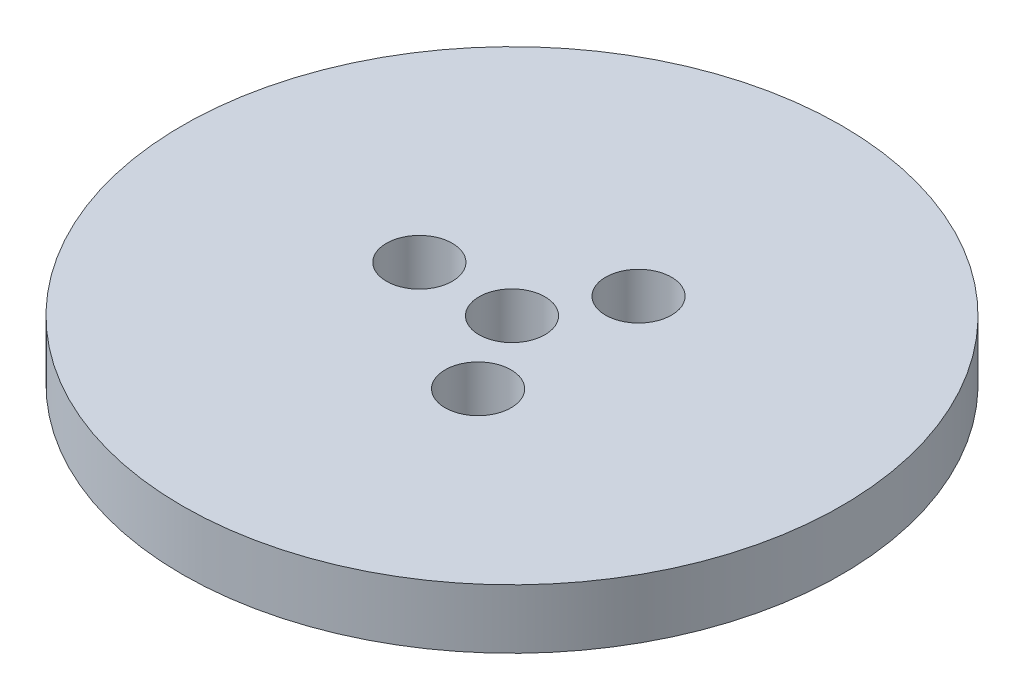
SolidWorks part; units mm, degrees
ref_plane "Front Plane" through (0, 0, 0) normal (0, 0, 1) x (1, 0, 0)
ref_plane "Top Plane" through (0, 0, 0) normal (0, 1, 0) x (1, 0, 0)
ref_plane "Right Plane" through (0, 0, 0) normal (1, 0, 0) x (0, 0, -1)
sketch "Sketch1" plane through (0, 0, 0) normal (0, 1, 0) x (1, 0, 0)
  circle A0 centre (0, 0) radius 100
  dimension "FLANGE_OD" = 200
extrude "Boss-Extrude1" add sketch "Sketch1" along normal blind 18
sketch "Sketch2" plane through (0, 0, 0) normal (0, 1, 0) x (1, 0, 0)
  circle A0 centre (0, 0) radius 10
  dimension "BORE_D" = 20
extrude "Cut-Extrude1" cut sketch "Sketch2" along normal through all
sketch "Sketch3" plane through (0, 18, 0) normal (0, 1, 0) x (1, 0, 0)
  circle A0 centre (0, 0) radius 28.1087 construction
  circle A1 centre (-28.1087, 0) radius 10
  dimension "BOLT_D" = 20
  dimension "BOLT_PCD" = 56.2175
extrude "Cut-Extrude2" cut sketch "Sketch3" against normal blind 15.0805
pattern_circular "CirPattern1" count 3 over 360 about axis through (0, 0, 0) along (0, 1, 0) of "Cut-Extrude2"
